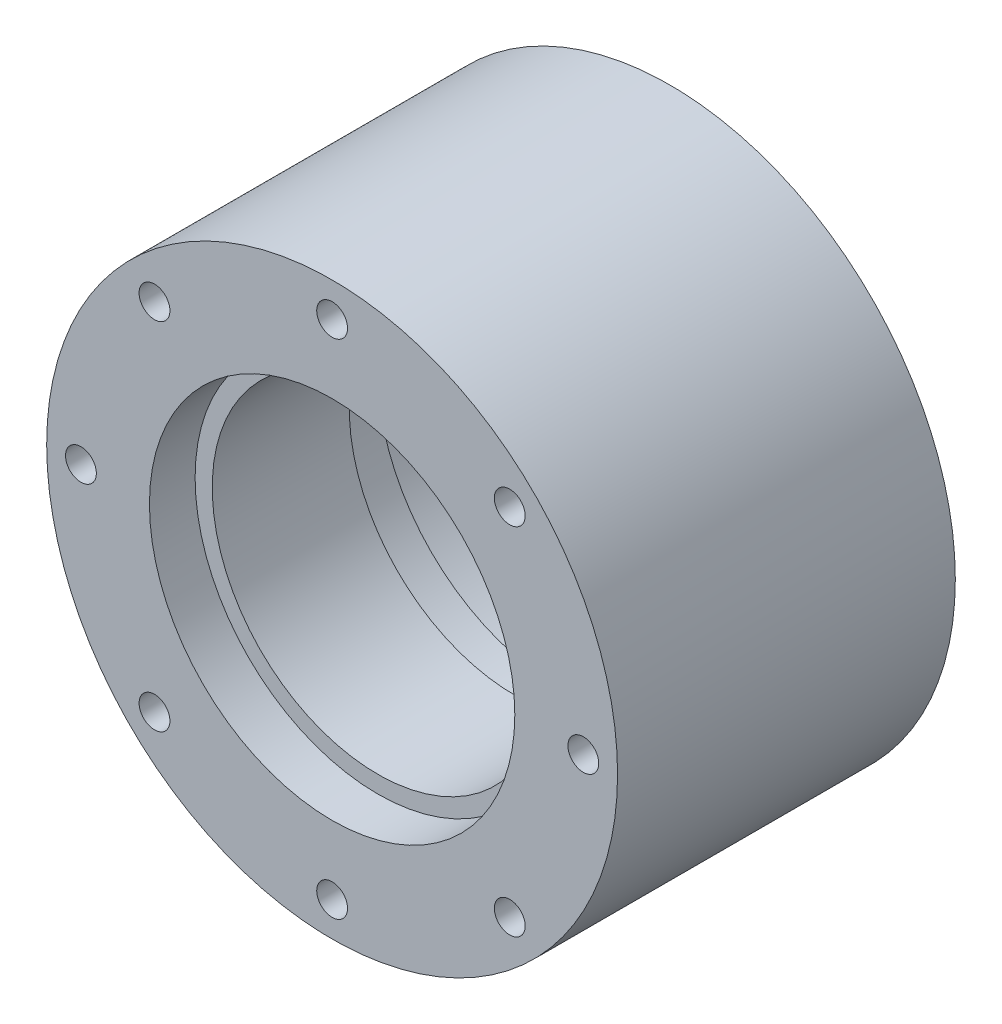
SolidWorks part; units mm, degrees
ref_plane "Front Plane" through (0, 0, 0) normal (0, 0, 1) x (1, 0, 0)
ref_plane "Top Plane" through (0, 0, 0) normal (0, 1, 0) x (1, 0, 0)
ref_plane "Right Plane" through (0, 0, 0) normal (1, 0, 0) x (0, 0, -1)
ref_axis "Z" through (0, 0, 11.479) along (0, 0, -1)
sketch "Sketch7" plane through (0, 0, 0) normal (0, 1, 0) x (1, 0, 0)
  line L0 (16, 10) -> (16, 6)
  line L2 (16, 6) -> (14.5, 6)
  line L3 (16, 10) -> (19, 10)
  line L4 (19, 10) -> (19, 19.58)
  line L5 (19, 19.58) -> (25, 19.58)
  line L6 (25, 19.58) -> (25, -10)
  line L7 (24.7452, 0) -> (-6.4078, 0) construction
  line L8 (16, -6) -> (14.5, -6)
  line L9 (16, -10) -> (16, -6)
  line L10 (14.5, 6) -> (14.5, -6)
  line L11 (25, -10) -> (16, -10)
  line L12 (0, -11.479) -> (0, 21.059) construction
  dimension "D2" = 4
  dimension "D4" = 6
  dimension "D6" = 6
  dimension "D7" = 9.58
  dimension "D1" = 14.5
  dimension "D3" = 16
  dimension "D5" = 25
revolve "Revolve1" add sketch "Sketch7" angle 360 about axis through (0, 0, 11.479) along (0, 0, -1)
sketch "Sketch3" plane through (0, 0, 0) normal (0, 0, 1) x (1, 0, 0)
  line L1 (0, 25) -> (0, 19) construction
  circle A0 centre (0, 22) radius 1.35
  circle A1 centre (0, 0) radius 25 construction
  circle A6 centre (0, 0) radius 19 construction
  point P2 (0, 0)
  point P9 (0, 0)
  point P10 (0, 18.629)
  dimension "D1" = 2.7
extrude "Cut-Extrude2" cut sketch "Sketch3" against normal through all both and the other way through all
sketch "Sketch4" plane through (0, 0, -10) normal (0, 0, -1) x (-1, 0, 0)
  circle A0 centre (0, 22) radius 2.25
  circle A1 centre (0, 22) radius 1.35 construction
  dimension "D1" = 4.5
extrude "Cut-Extrude4" cut sketch "Sketch4" against normal blind 2.5 and the other way through all
chamfer "Chamfer1" distance 0.1 angle 45 1 edges at (-1.35, 22, -7.5)
pattern_circular "CirPattern3" count 4 over 360 about axis through (0, 0, 11.479) along (0, 0, -1) of "Cut-Extrude4"
pattern_circular "CirPattern2" count 8 over 360 about axis through (0, 0, 11.479) along (0, 0, -1) of "Cut-Extrude2"
ref_plane "Plane1" through (0, 0, -14.79) normal (0, 0, -1) x (-1, 0, 0)
ref_plane "Plane2" through (0, 0, 0) normal (0.9239, 0.3827, 0) x (0, 0, -1)
sketch "Sketch8" plane through (0, 0, 0) normal (0, 0, 1) x (1, 0, 0)
  line L0 (0, 0) -> (-7.271, 17.5537) construction
  line L1 (3.4729, -8.3842) -> (-3.4729, 8.3842) construction
  dimension "D1" = 19
ref_plane "Plane3" through (-7.271, 17.5537, 0) normal (0.3827, -0.9239, 0) x (-0.9239, -0.3827, 0)
equation "\"BearingBaseDistance\"= 12"
equation "\"BearingOD\"= 32"
equation "\"BearingHeight\"= 4"
equation "\"SeatsOD\"= \"BearingOD\" + 10"
equation "\"D3@Sketch7\"=\"BearingOD\"/2"
equation "\"D4@Sketch7\"=\"BearingBaseDistance\"/2"
equation "\"WireHarnessHeight\"= 0.05in * 4 + 4.5"
equation "\"D7@Sketch7\"=\"WireHarnessHeight\""
equation "\"OuterWallWidth\"= 6"
equation "\"D6@Sketch7\"=\"OuterWallWidth\""
equation "\"OverallOD\" = 50"
equation "\"D5@Sketch7\"=\"OverallOD\"/2"
equation "\"D1@Sketch8\"=(\"OverallOD\"-2*\"OuterWallWidth\")/2"
